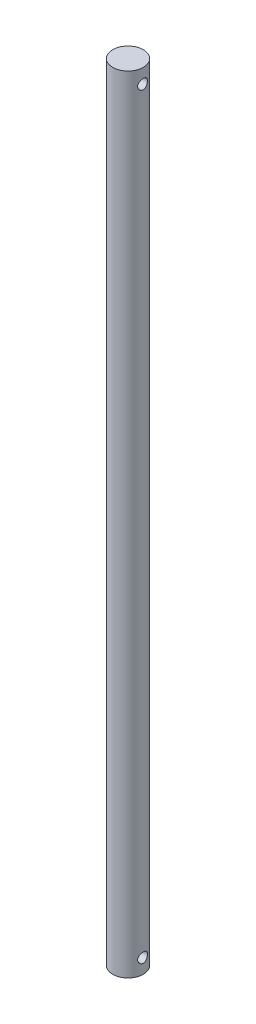
SolidWorks part; units mm, degrees
ref_plane "Front Plane" through (0, 0, 0) normal (0, 0, 1) x (1, 0, 0)
ref_plane "Top Plane" through (0, 0, 0) normal (0, 1, 0) x (1, 0, 0)
ref_plane "Right Plane" through (0, 0, 0) normal (1, 0, 0) x (0, 0, -1)
sketch "Sketch1" plane through (0, 0, 0) normal (0, 1, 0) x (1, 0, 0)
  circle A0 centre (0, 0) radius 9.906
  dimension "D1" = 19.812
extrude "Boss-Extrude1" add sketch "Sketch1" along normal blind 508
sketch "Sketch2" plane through (0, 0, 0) normal (1, 0, 0) x (0, 0, -1)
  line L0 (9.906, 508) -> (-9.906, 508) construction
  line L6 (-9.906, 508) -> (-9.906, 0) construction
  circle A0 centre (0, 498.602) radius 3.175
  point P4 (0, 0)
  dimension "D2" = 6.35
  dimension "D1" = 9.398
  dimension "D3" = 9.906
extrude "Cut-Extrude1" cut sketch "Sketch2" against normal blind 22.86 from offset 20.32
ref_plane "Plane1" through (0, 254, 0) normal (0, 1, 0) x (1, 0, 0)
mirror "Mirror1" about plane through (0, 254, 0) normal (0, 1, 0) of "Cut-Extrude1"
